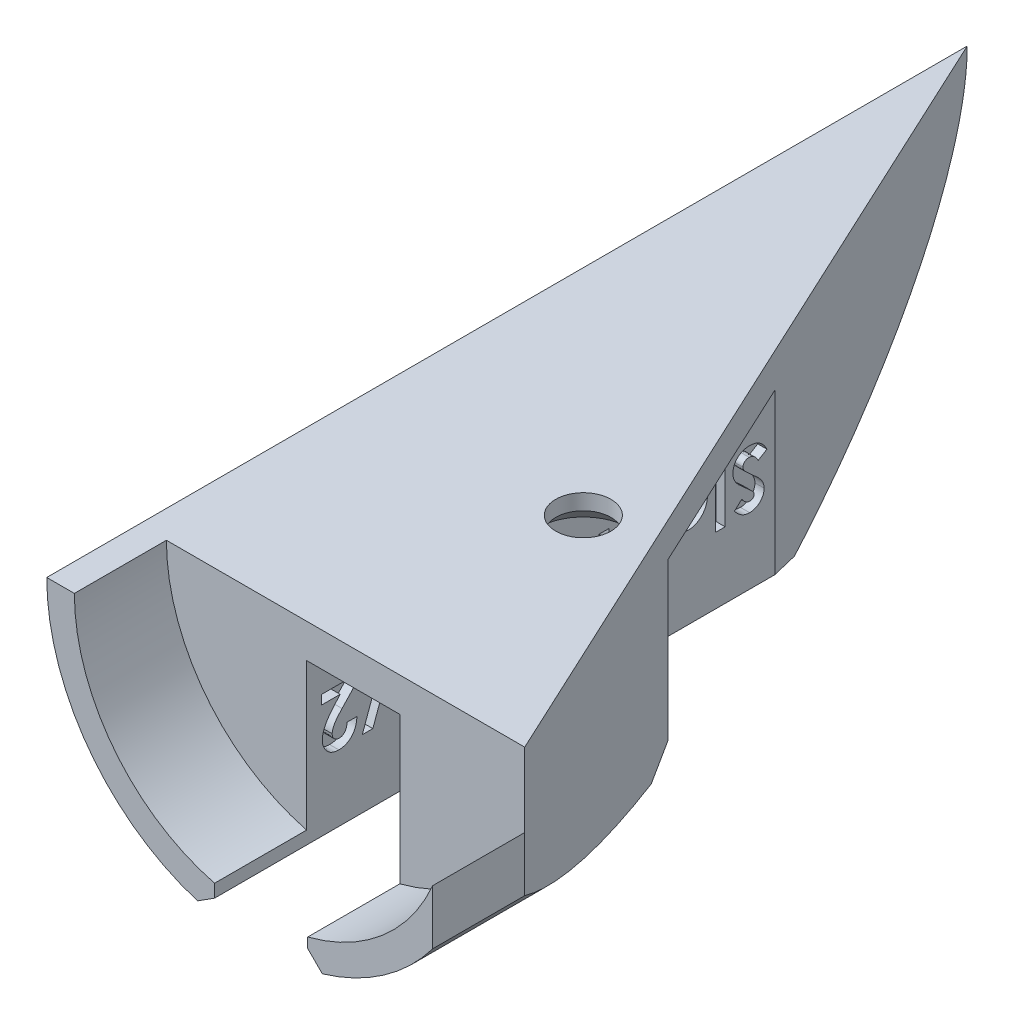
SolidWorks part; units mm, degrees
ref_plane "Front Plane" through (0, 0, 0) normal (0, 0, 1) x (1, 0, 0)
ref_plane "Top Plane" through (0, 0, 0) normal (0, 1, 0) x (1, 0, 0)
ref_plane "Right Plane" through (0, 0, 0) normal (1, 0, 0) x (0, 0, -1)
sketch "Sketch1" plane through (0, 0, 0) normal (0, 0, 1) x (1, 0, 0)
  line L1 (-14.7902, 8.509) -> (14.7902, 8.509)
  line L2 (3.0226, 5.969) -> (-3.0226, 5.969) construction
  line L11 (3.2131, -6.1595) -> (3.2131, 6.1595)
  line L12 (3.2131, 6.1595) -> (-3.2131, 6.1595)
  line L13 (-3.2131, 6.1595) -> (-3.2131, -6.1595)
  line L14 (-3.2131, -6.1595) -> (3.2131, -6.1595)
  line L15 (3.2131, -6.1595) -> (3.2131, 6.1595)
  line L16 (3.2131, 6.1595) -> (-3.2131, 6.1595)
  line L17 (-3.2131, 6.1595) -> (-3.2131, -6.1595)
  line L18 (-3.2131, -6.1595) -> (3.2131, -6.1595)
  arc A0 (-14.7902, 8.509) -> (14.7902, 8.509) centre (0, 8.509) ccw
  dimension "D1" = 2.54
  dimension "D2" = 0.1905
extrude "Boss-Extrude1" add sketch "Sketch1" along normal mid plane 190.5 contours L1 A0 L17 L16 L15 region at (0, 8.1798, 0)
sketch "Sketch2" plane through (0, 0, 95.25) normal (0, 0, 1) x (1, 0, 0)
  line L0 (-14.7902, 8.509) -> (14.7902, 8.509) construction
  line L1 (-12.8852, 8.509) -> (12.8852, 8.509)
  circle A0 centre (0, 8.509) radius 12.8852
  arc A2 (-14.7902, 8.509) -> (-3.2131, -5.9279) centre (0, 8.509) ccw construction
  line M2 (14.7902, 8.509) -> (-14.7902, 8.509)
  line M4 (-3.2131, -5.9279) -> (-3.2131, 6.1595)
  line M5 (-3.2131, 6.1595) -> (3.2131, 6.1595)
  line M6 (3.2131, 6.1595) -> (3.2131, -5.9279)
  dimension "D1" = 1.905
extrude "Cut-Extrude1" cut sketch "Sketch2" against normal blind 6.35 contours A0 M2 M4 M5 M6 region at (0, 8.2227, 95.25)
sketch "Sketch3" plane through (0, 0, -95.25) normal (0, 0, -1) x (-1, 0, 0)
  line L8 (12.8852, 8.509) -> (-12.8852, 8.509)
  line L9 (3.2131, 6.1595) -> (3.2131, -3.9691)
  line L10 (-3.2131, 6.1595) -> (3.2131, 6.1595)
  line L11 (-3.2131, -3.9691) -> (-3.2131, 6.1595)
  line L12 (12.8852, 8.509) -> (-12.8852, 8.509)
  line L13 (3.2131, 6.1595) -> (3.2131, -3.9691)
  line L14 (-3.2131, 6.1595) -> (3.2131, 6.1595)
  line L15 (-3.2131, -3.9691) -> (-3.2131, 6.1595)
  line L16 (14.7902, 8.509) -> (-14.7902, 8.509)
  line L17 (-3.2131, -5.9279) -> (-3.2131, 6.1595)
  line L18 (-3.2131, 6.1595) -> (3.2131, 6.1595)
  line L19 (3.2131, 6.1595) -> (3.2131, -5.9279)
  line L20 (14.7902, 8.509) -> (-14.7902, 8.509)
  line L21 (-3.2131, -5.9279) -> (-3.2131, 6.1595)
  line L22 (-3.2131, 6.1595) -> (3.2131, 6.1595)
  line L23 (3.2131, 6.1595) -> (3.2131, -5.9279)
  circle A2 centre (0, 8.509) radius 12.5042
  arc A4 (3.2131, -3.9691) -> (12.8852, 8.509) centre (0, 8.509) ccw
  arc A5 (-12.8852, 8.509) -> (-3.2131, -3.9691) centre (0, 8.509) ccw
  arc A6 (3.2131, -3.9691) -> (12.8852, 8.509) centre (0, 8.509) ccw
  arc A7 (-12.8852, 8.509) -> (-3.2131, -3.9691) centre (0, 8.509) ccw
  arc A9 (-14.7902, 8.509) -> (-3.2131, -5.9279) centre (0, 8.509) ccw
  arc A10 (3.2131, -5.9279) -> (14.7902, 8.509) centre (0, 8.509) ccw
  arc A11 (-14.7902, 8.509) -> (-3.2131, -5.9279) centre (0, 8.509) ccw
  arc A12 (3.2131, -5.9279) -> (14.7902, 8.509) centre (0, 8.509) ccw
  line M14 (14.7902, 8.509) -> (-14.7902, 8.509)
  arc M15 (-14.7902, 8.509) -> (-3.2131, -5.9279) centre (0, 8.509) ccw
  line M16 (-3.2131, -5.9279) -> (-3.2131, 6.1595)
  line M18 (3.2131, 6.1595) -> (3.2131, -5.9279)
  arc M19 (3.2131, -5.9279) -> (14.7902, 8.509) centre (0, 8.509) ccw
  dimension "D2" = 0.381
  dimension "D1" = 0
  dimension "D3" = 0
extrude "Cut-Extrude2" cut sketch "Sketch3" against normal blind 5.969 contours A6 M18 M19 M14 | A7 M14 M15 M16 | A7 A2 M14 M16 | L23 A6 A2 M14 region at (-10.0592, 0.7119, -95.25) region at (-13.8377, 8.3239, -95.25) region at (10.0381, 0.7912, -95.25) region at (10.3303, 0.5018, -95.25)
sketch "Sketch4" plane through (0, 6.1595, 0) normal (0, -1, 0) x (1, 0, 0)
  line L1 (0, -95.25) -> (0, 88.9) construction
  line L2 (3.2131, -95.25) -> (-3.2131, -95.25) construction
  line L3 (-3.2131, 88.9) -> (3.2131, 88.9) construction
  line L4 (0, -3.175) -> (-3.2131, -3.175) construction
  line L5 (-3.2131, 88.9) -> (-3.2131, -95.25) construction
  circle A0 centre (0, -79.375) radius 1.905
  circle A1 centre (0, 73.025) radius 1.905
  circle A2 centre (0, -3.175) radius 1.905
  dimension "D1" = 3.81
  dimension "D2" = 76.2
extrude "Cut-Extrude3" cut sketch "Sketch4" against normal through all
chamfer "Chamfer1" distance 1.27 angle 45 2 edges at (3.2131, -5.9279, 2.9845) (-3.2131, -5.9279, 2.9845) first distance on face at (3.2131, -1.8282, -0.0952) first distance on face at (-10.27, 0.2734, 2.9845)
chamfer "Chamfer2" distance 1.27 angle 45 3 edges at (0, 6.1595, 74.93) (0, 6.1595, -81.28) (0, 6.1595, -5.08)
sketch "Sketch6" plane through (0, 8.509, 0) normal (0, 1, 0) x (1, 0, 0)
  line L0 (-14.7902, -31.75) -> (14.7902, -95.25)
  line L1 (-14.7902, -95.25) -> (-14.7902, 89.281) construction
  line L2 (14.7902, -95.25) -> (14.7902, 89.281) construction
  line L3 (-14.7902, -95.25) -> (-12.8852, -95.25) construction
  line L5 (14.7902, -95.25) -> (14.7902, 89.281)
  line L6 (11.8321, -88.9) -> (11.8321, -95.25)
  line L7 (11.8321, -95.25) -> (12.8852, -95.25)
  line L17 (14.7902, 89.281) -> (12.5042, 89.281)
  line L18 (12.5042, 89.281) -> (12.5042, 95.25)
  line L19 (12.5042, 95.25) -> (-12.5042, 95.25)
  line L20 (-12.5042, 95.25) -> (-12.5042, 89.281)
  line L21 (-12.5042, 89.281) -> (-14.7902, 89.281)
  line L22 (-14.7902, 89.281) -> (-14.7902, -95.25)
  line L23 (-14.7902, -95.25) -> (-12.8852, -95.25)
  line L24 (-12.8852, -95.25) -> (-12.8852, -88.9)
  line L25 (-12.8852, -88.9) -> (12.8852, -88.9)
  line L26 (12.8852, -88.9) -> (12.8852, -95.25)
  line L27 (12.8852, -95.25) -> (14.7902, -95.25)
  line L28 (14.7902, -95.25) -> (14.7902, 89.281)
  line L29 (14.7902, 89.281) -> (12.5042, 89.281)
  line L30 (12.5042, 89.281) -> (12.5042, 95.25)
  line L31 (12.5042, 95.25) -> (-12.5042, 95.25)
  line L32 (-12.5042, 95.25) -> (-12.5042, 89.281)
  line L33 (-12.5042, 89.281) -> (-14.7902, 89.281)
  line L34 (-14.7902, 89.281) -> (-14.7902, -95.25)
  line L35 (-14.7902, -95.25) -> (-12.8852, -95.25)
  line L36 (-12.8852, -95.25) -> (-12.8852, -88.9)
  line L37 (-12.8852, -88.9) -> (11.8321, -88.9)
  line L38 (12.8852, -91.1605) -> (12.8852, -95.25)
  line L39 (12.8852, -95.25) -> (14.7902, -95.25)
  circle M13 centre (0, 79.375) radius 1.905
  circle M15 centre (0, 3.175) radius 1.905
  line M16 (14.7902, 89.281) -> (12.5042, 89.281)
  line M17 (12.5042, 89.281) -> (12.5042, 95.25)
  line M18 (12.5042, 95.25) -> (-12.5042, 95.25)
  line M19 (-12.5042, 95.25) -> (-12.5042, 89.281)
  line M20 (-12.5042, 89.281) -> (-14.7902, 89.281)
  line M21 (-14.7902, 89.281) -> (-14.7902, -95.25)
  line M24 (-12.8852, -88.9) -> (12.8852, -88.9)
  line M25 (12.8852, -88.9) -> (12.8852, -95.25)
  line M26 (12.8852, -95.25) -> (14.7902, -95.25)
  line M27 (14.7902, -95.25) -> (14.7902, 89.281)
  dimension "D1" = 63.5
  dimension "D3" = 0
extrude "Cut-Extrude5" cut sketch "Sketch6" against normal through all contours L0 M21 M27 M16 M17 M18 M19 M20 M13 M15 | L0 M24 M25 | L6 L7 L0 M25 | L0 M25 M26 region at (0.9937, 8.509, -14.2585) region at (12.5341, 8.509, 89.6535) region at (12.3206, 8.509, 92.5993) region at (13.5202, 8.509, 93.8868)
sketch "Sketch7" plane through (-3.2131, 0, 0) normal (1, 0, 0) x (0, 0, -1)
  line L0 (-56.6024, 3.6195) -> (-88.9, 3.6195) construction
  line L1 (-56.6024, 6.1595) -> (-56.6024, -4.8637) construction
  line L2 (-88.9, -3.9691) -> (-88.9, 6.1595) construction
  line L3 (-88.9, 6.1595) -> (-56.6024, 6.1595) construction
  text T0 "<b>Slant End V2</b>\r\n" font "Century Gothic" height 3.81
  dimension "D1" = 2.54
extrude "Cut-Extrude6" cut sketch "Sketch7" against normal blind 0.635
sketch "Sketch5" plane through (-3.2131, 0, 0) normal (1, 0, 0) x (0, 0, -1)
  line L0 (53.2413, 3.6195) -> (-53.2413, 3.6195) construction
  line L1 (-88.9, 6.1595) -> (-56.6024, 6.1595) construction
  text T0 "<b>Ceiling LED Mount V1</b>" font "Century Gothic" height 3.81
  point P2 (0, 3.6195)
  dimension "D1" = 2.54
